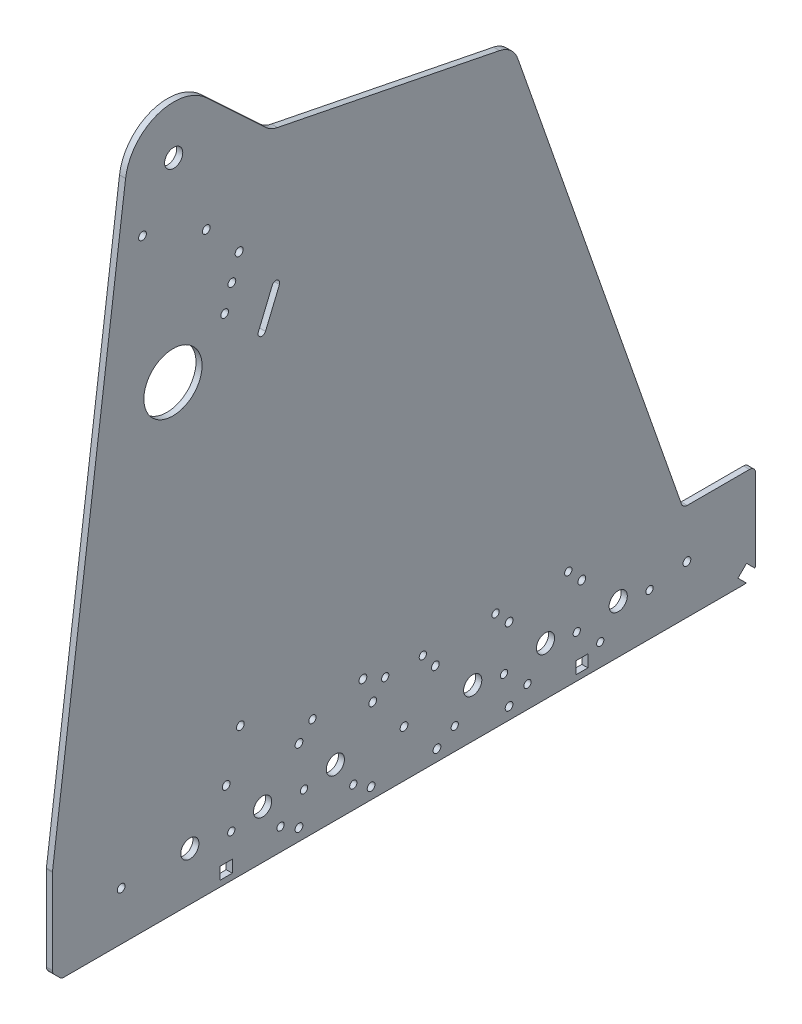
SolidWorks part; units mm, degrees
ref_plane "Front Plane" through (0, 0, 0) normal (0, 0, 1) x (1, 0, 0)
ref_plane "Top Plane" through (0, 0, 0) normal (0, 1, 0) x (1, 0, 0)
ref_plane "Right Plane" through (0, 0, 0) normal (1, 0, 0) x (0, 0, -1)
sketch "Sketch1" plane through (0, 0, 0) normal (1, 0, 0) x (0, 0, -1)
  line L0 (-184.15, -24.6062) -> (184.15, -24.6062)
  line L1 (184.15, -24.6062) -> (184.15, 26.1938)
  line L2 (184.15, 26.1938) -> (146.05, 26.1937)
  line L3 (146.05, 26.1937) -> (57.15, 280.1938)
  line L5 (-145.839, 321.5609) -> (-184.15, 26.1938)
  line L6 (-184.15, 26.1938) -> (-184.15, -24.6062)
  line L7 (-184.15, 350.0437) -> (184.15, 350.0437) construction
  line L8 (57.15, 280.1938) -> (-69.85, 305.5938)
  line L9 (-69.85, 305.5938) -> (-103.3099, 336.854)
  arc A0 (-103.3099, 336.854) -> (-145.839, 321.5609) centre (-120.65, 318.2937) ccw
  point P8 (0, -24.6062)
  dimension "D1" = 368.3
  dimension "D7" = 25.4
  dimension "D2" = 50.8
  dimension "D3" = 38.1
  dimension "D4" = 24.6062
  dimension "D5" = 374.65
  dimension "D6" = 304.8
  dimension "D8" = 342.9
  dimension "D9" = 127
  dimension "D10" = 304.8
  dimension "D11" = 25.4
  dimension "D12" = 127
extrude "Boss-Extrude1" add sketch "Sketch1" along normal blind 3.175
chamfer "Chamfer1" distance 4.7625 angle 45 2 edges at (1.5875, -24.6062, 184.15) (1.5875, -24.6062, -184.15)
fillet "Fillet1" radius 12.7 2 edges at (1.5875, 305.5938, 69.85) (1.5875, 280.1938, -57.15)
fillet "Fillet2" radius 3.175 3 edges at (1.5875, 26.1938, 184.15) (1.5875, 26.1938, -184.15) (1.5875, 26.1937, -146.05)
fillet "Fillet3" radius 3.175 4 edges at (1.5875, -19.8438, -184.15) (1.5875, -24.6062, -179.3875) (1.5875, -19.8437, 184.15) (1.5875, -24.6062, 179.3875)
sketch "Sketch16" plane through (3.175, 0, 0) normal (1, 0, 0) x (0, 0, -1)
  circle A0 centre (112.1746, 0.7937) radius 4.7625
  circle A1 centre (74.0746, 0.7937) radius 4.7625
  circle A2 centre (35.9746, 0.7937) radius 4.7625
  circle A3 centre (-35.9746, 0.7938) radius 4.7625
  circle A4 centre (-74.0746, 0.7938) radius 4.7625
  circle A5 centre (-112.1746, 0.7937) radius 4.7625
  dimension "D1" = 9.525
  dimension "D2" = 9.525
extrude "Cut-Extrude1" cut sketch "Sketch16" against normal up to next
sketch "Sketch25" plane through (3.175, 0, 0) normal (1, 0, 0) x (0, 0, -1)
  circle A0 centre (102.7672, -13.0003) radius 1.905 construction
  circle A1 centre (86.0486, 27.3622) radius 1.905 construction
  circle A2 centre (128.5804, -2.3081) radius 1.905 construction
  circle A3 centre (102.7672, -13.0003) radius 1.905
  circle A4 centre (86.0486, 27.3622) radius 1.905
  circle A5 centre (128.5804, -2.3081) radius 1.905
  circle A6 centre (64.6672, -13.0003) radius 1.905 construction
  circle A8 centre (-9.8486, 27.3622) radius 1.905 construction
  circle A10 centre (-47.9486, 27.3622) radius 1.905 construction
  circle A11 centre (-90.4804, -2.3081) radius 1.905 construction
  circle A12 centre (-64.6672, -13.0003) radius 1.905 construction
  circle A14 centre (-52.3804, -2.3081) radius 1.905 construction
  circle A15 centre (-26.5672, -13.0003) radius 1.905 construction
  circle A16 centre (9.8486, 27.3622) radius 1.905 construction
  circle A17 centre (26.5672, -13.0003) radius 1.905 construction
  circle A18 centre (47.9486, 27.3622) radius 1.905 construction
  circle A19 centre (52.3804, -2.3081) radius 1.905 construction
  circle A20 centre (90.4804, -2.3081) radius 1.905 construction
  circle A21 centre (-9.8486, 27.3622) radius 1.905
  circle A23 centre (-47.9486, 27.3622) radius 1.905
  circle A24 centre (-90.4804, -2.3081) radius 1.905
  circle A25 centre (-64.6672, -13.0003) radius 1.905
  circle A27 centre (-52.3804, -2.3081) radius 1.905
  circle A28 centre (-26.5672, -13.0003) radius 1.905
  circle A29 centre (9.8486, 27.3622) radius 1.905
  circle A30 centre (26.5672, -13.0003) radius 1.905
  circle A31 centre (47.9486, 27.3622) radius 1.905
  circle A32 centre (64.6672, -13.0003) radius 1.905
  circle A33 centre (52.3804, -2.3081) radius 1.905
  circle A34 centre (90.4804, -2.3081) radius 1.905
extrude "Cut-Extrude4" cut sketch "Sketch25" against normal up to next
sketch "Sketch23" plane through (3.175, 0, 0) normal (1, 0, 0) x (0, 0, -1)
  point P0 (-55.0246, -18.3223)
  point P3 (-55.0246, 19.9098)
  point P6 (-93.1246, 19.9098)
  point P9 (-17.2515, -18.6426)
  point P12 (-16.4124, 19.3854)
  point P15 (16.4124, 19.3854)
  point P18 (17.2515, -18.6426)
  point P21 (55.0246, -18.3223)
  point P27 (93.1246, 19.9098)
  point P30 (55.0246, 19.9098)
hole_wizard "#8 (0.16) Diameter Hole1" positions "Sketch23" profile "Sketch24" hole size "#8" standard "ANSI Inch" end condition up to next
sketch "Sketch24" plane through (3.175, -18.3223, 55.0246) normal (0, 1, 0) x (0, 0, -1)
  line L0 (0, 0) -> (0, 3.175)
  line L1 (0, 3.175) -> (2.032, 3.175)
  line L2 (2.032, 3.175) -> (2.032, 0)
  line L5 (2.032, 0) -> (0, 0)
  line L11 (0, -6.35) -> (0, 107.95) construction
  dimension "Thru Hole Dia." = 4.064
  dimension "Thru Hole Depth" = 3.175
sketch "Sketch22" plane through (3.175, 0, 0) normal (1, 0, 0) x (0, 0, -1)
  line L0 (-96.2996, -15.1473) -> (-89.9496, -15.1473) construction
  line L1 (-96.2996, -15.1473) -> (-89.9496, -15.1473)
  line L2 (-96.2996, -15.1473) -> (-96.2996, -21.4973)
  line L3 (-96.2996, -21.4973) -> (-89.9496, -21.4973)
  line L4 (-89.9496, -15.1473) -> (-89.9496, -21.4973)
  line L5 (-96.2996, -15.1473) -> (-89.9496, -21.4973) construction
  line L6 (-96.2996, -21.4973) -> (-89.9496, -15.1473) construction
  line L7 (-89.9496, -15.1473) -> (-89.9496, -19.8734) construction
  line L77 (179.3875, -24.6062) -> (183.8776, -20.1161)
  line L78 (179.3875, -24.6062) -> (174.8974, -20.1161)
  line L79 (183.8776, -20.1161) -> (179.3875, -15.626)
  line L80 (174.8974, -20.1161) -> (179.3875, -15.626)
  line L81 (180.3174, -23.6763) -> (183.2201, -20.7737) construction
  line L82 (-178.0724, -24.6062) -> (178.0724, -24.6062) construction
  line L84 (89.9496, -21.4973) -> (96.2996, -21.4973)
  line L85 (89.9496, -21.4973) -> (89.9496, -15.1473)
  line L86 (89.9496, -15.1473) -> (96.2996, -15.1473)
  line L87 (96.2996, -21.4973) -> (96.2996, -15.1473)
  line L88 (89.9496, -21.4973) -> (96.2996, -15.1473) construction
  line L89 (89.9496, -15.1473) -> (96.2996, -21.4973) construction
  point P0 (-93.1246, -18.3223)
  point P19 (93.1246, -18.3223)
  dimension "D1" = 6.35
  dimension "D2" = 6.35
extrude "Cut-Extrude3" cut sketch "Sketch22" against normal up to next
sketch "Sketch21" plane through (3.175, 0, 0) normal (1, 0, 0) x (0, 0, -1)
  circle A0 centre (-148.1579, 0.7937) radius 2.032
  circle A2 centre (0, 0) radius 2.032
  circle A3 centre (148.1579, 0.7938) radius 2.032
  dimension "D1" = 4.064
extrude "Cut-Extrude2" cut sketch "Sketch21" against normal up to next
sketch "Sketch26" plane through (3.175, 0, 0) normal (1, 0, 0) x (0, 0, -1)
  line L0 (-145.839, 321.5609) -> (-184.1236, 26.3971) construction
  line L1 (-178.0724, -24.6062) -> (178.0724, -24.6062) construction
  circle A0 centre (-121.0218, 216.6937) radius 15.24
  dimension "D1" = 30.48
  dimension "D2" = 38.1
  dimension "D3" = 241.3
extrude "Cut-Extrude5" cut sketch "Sketch26" against normal through all
sketch "Sketch27" plane through (3.175, 0, 0) normal (1, 0, 0) x (0, 0, -1)
  circle A0 centre (-120.65, 318.2937) radius 4.7625
  dimension "D1" = 9.525
extrude "Cut-Extrude6" cut sketch "Sketch27" against normal through all
sketch "Sketch28" plane through (3.175, 0, 0) normal (1, 0, 0) x (0, 0, -1)
  line L0 (-120.65, 318.2937) -> (-103.5612, 277.2599) construction
  line L1 (-103.5612, 277.2599) -> (-86.3654, 258.566) construction
  line L2 (-86.3654, 258.566) -> (-90.1612, 246.4465) construction
  line L3 (-90.1612, 246.4465) -> (-93.9569, 234.327) construction
  line L4 (-145.839, 321.5609) -> (-184.1236, 26.3971) construction
  circle A0 centre (-93.9569, 234.327) radius 2.032
  circle A1 centre (-90.1612, 246.4465) radius 2.032
  circle A2 centre (-86.3654, 258.566) radius 2.0955
  circle A3 centre (-103.5612, 277.2599) radius 2.032
  dimension "D4" = 4.064
  dimension "D5" = 4.191
  dimension "D6" = 4.064
  dimension "D1" = 25.4
  dimension "D2" = 44.45
  dimension "D3" = 12.7
  dimension "D7" = 30
  dimension "D8" = 120
  dimension "D9" = 160
extrude "Cut-Extrude7" cut sketch "Sketch28" against normal through all
sketch "Sketch29" plane through (3.175, 0, 0) normal (1, 0, 0) x (0, 0, -1)
  line L0 (-145.839, 321.5609) -> (-184.1236, 26.3971) construction
  line L1 (-67.1375, 233.9197) -> (-74.4276, 216.3198) construction
  line L2 (-65.2602, 233.1421) -> (-72.5503, 215.5422)
  line L3 (-69.0148, 234.6973) -> (-76.305, 217.0974)
  line L4 (-67.1375, 233.9197) -> (-67.1375, 253.7354) construction
  circle A0 centre (-136.9875, 291.0697) radius 2.032
  circle A2 centre (-120.65, 318.2937) radius 4.7625 construction
  arc A4 (-65.2602, 233.1421) -> (-69.0148, 234.6973) centre (-67.1375, 233.9197) ccw
  arc A5 (-76.305, 217.0974) -> (-72.5503, 215.5422) centre (-74.4276, 216.3198) ccw
  point P8 (-70.7826, 225.1198)
  dimension "D1" = 31.75
  dimension "D2" = 4.064
  dimension "D3" = 69.85
  dimension "D4" = 12.7
  dimension "D5" = 57.15
  dimension "D6" = 19.05
  dimension "D7" = 22.5
extrude "Cut-Extrude8" cut sketch "Sketch29" against normal through all
sketch "Sketch30" plane through (3.175, 0, 0) normal (1, 0, 0) x (0, 0, -1)
  line L0 (-85.7125, 43.2475) -> (-21.5354, 32.3996) construction
  circle A1 centre (-21.5354, 32.3996) radius 7.9375 construction
  circle A2 centre (-85.7125, 43.2475) radius 2.032
  circle A3 centre (-35.9746, 0.7938) radius 4.7625 construction
  circle A4 centre (-48.1454, 36.8975) radius 19.05 construction
  circle A5 centre (-85.7125, 43.2475) radius 19.05 construction
  circle A6 centre (-21.5354, 32.3996) radius 2.032
  circle A7 centre (-74.0746, 0.7938) radius 4.7625 construction
  point P4 (-48.1454, 36.8975)
  dimension "D2" = 38.1
  dimension "D4" = 15.875
  dimension "D5" = 4.064
  dimension "D6" = 44.45
  dimension "D1" = 38.1
  dimension "D3" = 6.35
extrude "Cut-Extrude9" cut sketch "Sketch30" against normal through all
sketch "Sketch31" [suppressed] plane through (0, 0, 0) normal (-1, 0, 0) x (0, 0, 1)
  circle A0 centre (-19.05, 244.475) radius 2.032
  circle A1 centre (76.2, 254) radius 2.032
  dimension "D1" = 19.05
  dimension "D3" = 4.064
  dimension "D4" = 76.2
  dimension "D6" = 4.064
  dimension "D2" = 244.475
  dimension "D5" = 254
extrude "Cut-Extrude10" [suppressed] cut sketch "Sketch31" against normal through all
sketch "Sketch34" [suppressed] plane through (0, 0, 0) normal (-1, 0, 0) x (0, 0, 1)
  line L0 (44.45, 161.925) -> (-19.05, 244.475) construction
  line L1 (42.8394, 160.6861) -> (-20.6606, 243.2361)
  line L2 (46.0606, 163.1639) -> (-17.4394, 245.7139)
  arc A0 (42.8394, 160.6861) -> (46.0606, 163.1639) centre (44.45, 161.925) ccw
  arc A1 (-17.4394, 245.7139) -> (-20.6606, 243.2361) centre (-19.05, 244.475) ccw
  point P3 (12.7, 203.2)
  dimension "D5" = 2.032
  dimension "D1" = 161.925
  dimension "D2" = 44.45
  dimension "D3" = 244.475
  dimension "D4" = 19.05
extrude "Cut-Extrude12" [suppressed] cut sketch "Sketch34" against normal through all
